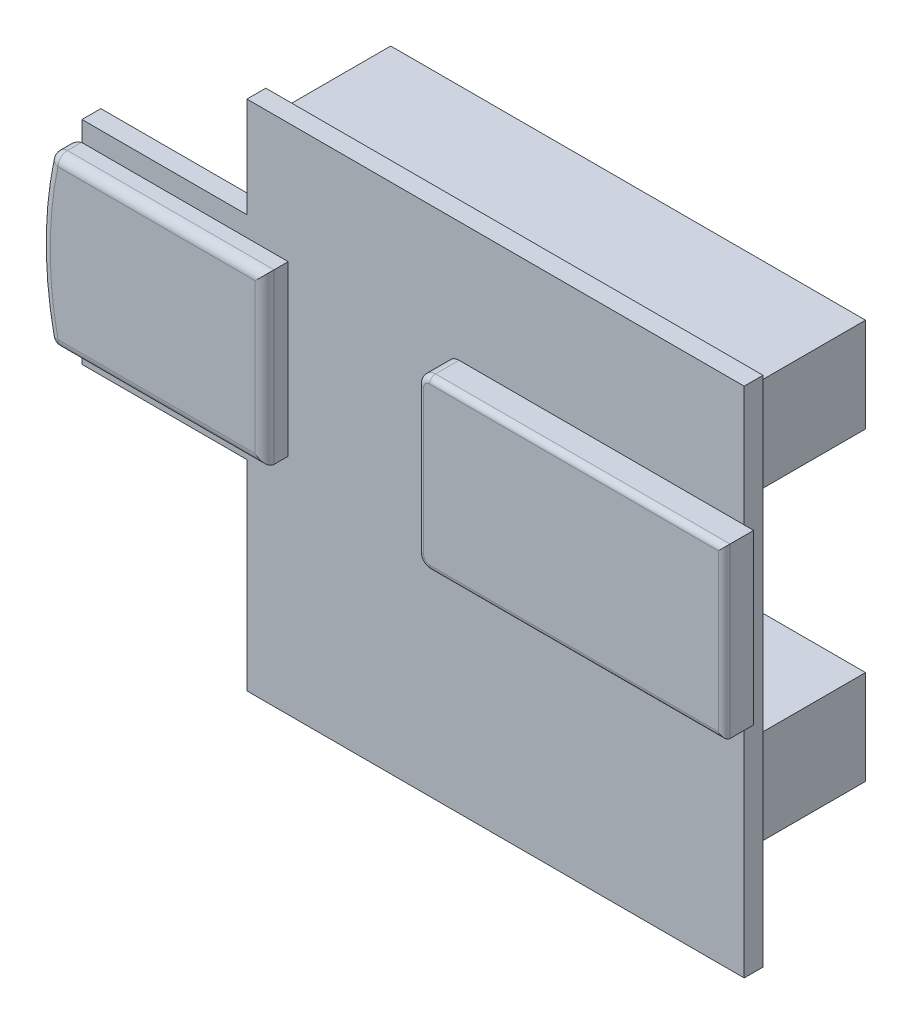
SolidWorks part; units mm, degrees
ref_plane "Front Plane" through (0, 0, 0) normal (0, 0, 1) x (1, 0, 0)
ref_plane "Top Plane" through (0, 0, 0) normal (0, 1, 0) x (1, 0, 0)
ref_plane "Right Plane" through (0, 0, 0) normal (1, 0, 0) x (0, 0, -1)
sketch "Sketch1" plane through (0, 0, 0) normal (0, 0, 1) x (1, 0, 0)
  line L0 (0, 17) -> (0, 0)
  line L1 (42.2, 43.5) -> (0, 43.5)
  line L2 (42.2, 43.5) -> (42.2, 0)
  line L3 (42.2, 0) -> (0, 0)
  line L4 (0, 43.5) -> (0, 35)
  line L5 (0, 35) -> (-14, 35)
  line L7 (0, 17) -> (-14, 17)
  line L8 (-14, 35) -> (-14, 17)
  dimension "D1" = 42.2
  dimension "D2" = 43.5
  dimension "D3" = 14
  dimension "D4" = 18
  dimension "D5" = 8.5
extrude "Extrude1" add sketch "Sketch1" along normal blind 1.6
sketch "Sketch2" plane through (0, 0, 0) normal (0, 0, -1) x (-1, 0, 0)
  line L0 (-42.2, 43.5) -> (0, 43.5) construction
  line L1 (-41.3, 42.3) -> (-1, 42.3)
  line L2 (-41.3, 42.3) -> (-41.3, 34.3)
  line L3 (-41.3, 34.3) -> (-1, 34.3)
  line L4 (-1, 42.3) -> (-1, 34.3)
  line L5 (-41.3, 16.4) -> (-1, 16.4)
  line L6 (-41.3, 16.4) -> (-41.3, 8.4)
  line L7 (-41.3, 8.4) -> (-1, 8.4)
  line L8 (-1, 16.4) -> (-1, 8.4)
  line L9 (0, 43.5) -> (0, 35) construction
  line L10 (0, 17) -> (0, 0) construction
  line L11 (0, 0) -> (-42.2, 0) construction
  dimension "D1" = 8
  dimension "D2" = 40.3
  dimension "D3" = 8
  dimension "D4" = 40.3
  dimension "D5" = 1.2
  dimension "D6" = 1
  dimension "D7" = 1
  dimension "D8" = 8.4
extrude "Extrude2" add sketch "Sketch2" along normal blind 9.6
sketch "Sketch3" plane through (0, 0, -9.6) normal (0, 0, -1) x (-1, 0, 0)
  line L0 (-1, 42.3) -> (-41.3, 42.3) construction
  line L1 (-40.15, 41.3) -> (-2.15, 41.3)
  line L2 (-40.15, 41.3) -> (-40.15, 35.3)
  line L3 (-40.15, 35.3) -> (-2.15, 35.3)
  line L4 (-2.15, 41.3) -> (-2.15, 35.3)
  line L5 (-40.15, 15.3) -> (-2.15, 15.3)
  line L6 (-40.15, 15.3) -> (-40.15, 9.3)
  line L7 (-40.15, 9.3) -> (-2.15, 9.3)
  line L8 (-2.15, 15.3) -> (-2.15, 9.3)
  line L9 (-1, 34.3) -> (-1, 42.3) construction
  line L10 (-1, 8.4) -> (-1, 16.4) construction
  dimension "D1" = 6
  dimension "D2" = 38
  dimension "D3" = 6
  dimension "D4" = 38
  dimension "D5" = 20
  dimension "D6" = 1
  dimension "D7" = 1.15
  dimension "D8" = 1.15
extrude "Cut-Extrude1" cut sketch "Sketch3" against normal blind 6.1
sketch "Sketch4" plane through (0, 0, 1.6) normal (0, 0, 1) x (1, 0, 0)
  line L0 (-14, 17) -> (0, 17) construction
  line L1 (3.5, 33.3) -> (-14.6778, 33.3)
  line L2 (3.5, 33.3) -> (3.5, 19)
  line L3 (3.5, 19) -> (-14.6778, 19)
  line L4 (3.5, 26.15) -> (22.4132, 26.15) construction
  line L5 (0, 43.5) -> (0, 35) construction
  line L6 (16, 26.15) -> (16, 37.055) construction
  arc A0 (-14.6778, 19) -> (-14.6778, 33.3) centre (16, 26.15) cw
  dimension "D2" = 16
  dimension "D5" = 31.5
  dimension "D1" = 14.3
  dimension "D3" = 2
  dimension "D4" = 3.5
extrude "Extrude3" add sketch "Sketch4" along normal blind 2
fillet "Fillet2" radius 0.8 7 edges at (-14.6778, 33.3, 2.6) (-15.5, 26.15, 3.6) (-14.6778, 19, 2.6) (-15.5, 26.15, 1.6) (-5.5889, 19, 3.6) (3.5, 26.15, 3.6) (-5.5889, 33.3, 3.6)
sketch "Sketch5" plane through (0, 0, 1.6) normal (0, 0, 1) x (1, 0, 0)
  line L0 (-13.8558, 19) -> (3.5, 19) construction
  line L1 (18, 19) -> (43, 19)
  line L2 (17, 20) -> (17, 32.3)
  line L3 (18, 33.3) -> (43, 33.3)
  line L4 (43, 19) -> (43, 33.3)
  line L5 (3.5, 33.3) -> (-13.8558, 33.3) construction
  line L6 (3.5, 19) -> (3.5, 33.3) construction
  arc A0 (17, 32.3) -> (18, 33.3) centre (18, 32.3) cw
  arc A1 (17, 20) -> (18, 19) centre (18, 20) ccw
  dimension "D3" = 1
  dimension "D1" = 13.5
  dimension "D2" = 26
extrude "Extrude4" add sketch "Sketch5" along normal blind 2.5
fillet "Fillet3" radius 0.5 6 edges at (30.5, 19, 4.1) (17.2929, 19.2929, 4.1) (17, 26.15, 4.1) (17.2929, 33.0071, 4.1) (30.5, 33.3, 4.1) (43, 26.15, 4.1)
